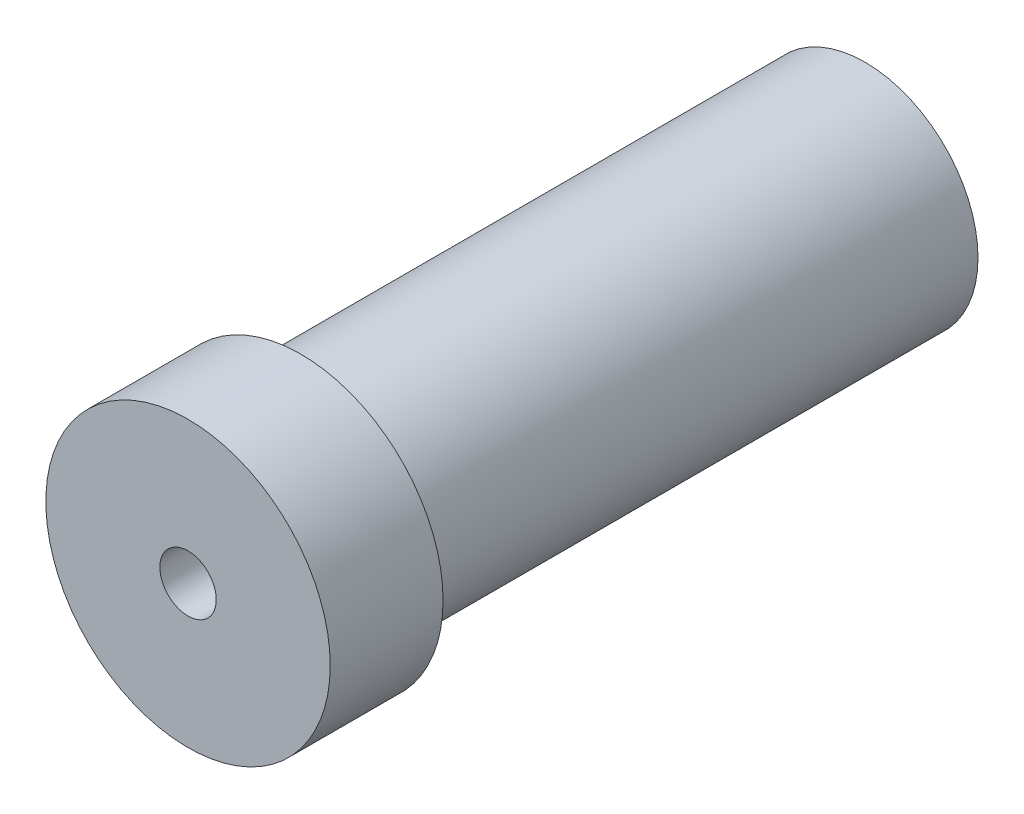
SolidWorks part; units mm, degrees
ref_plane "Front" through (0, 0, 0) normal (0, 0, 1) x (1, 0, 0)
ref_plane "Top" through (0, 0, 0) normal (0, 1, 0) x (1, 0, 0)
ref_plane "Right" through (0, 0, 0) normal (1, 0, 0) x (0, 0, -1)
sketch "Sketch3" plane through (0, 0, 0) normal (0, 0, 1) x (1, 0, 0)
  line L0 (0, -65.6804) -> (0, -71.4078) construction
  circle A0 centre (0, 0) radius 16.002
  circle A3 centre (0, 0) radius 3.175
  dimension "D1" = 32.004
  dimension "D2" = 6.35
extrude "Boss-Extrude1" add sketch "Sketch3" along normal blind 12.7
sketch "Sketch5" plane through (0, 0, 0) normal (0, 0, -1) x (-1, 0, 0)
  line L1 (0, 6.4158) -> (-5.5563, 3.2079)
  line L2 (-5.5563, 3.2079) -> (-5.5563, -3.2079)
  line L3 (-5.5563, -3.2079) -> (0, -6.4158)
  line L4 (0, -6.4158) -> (5.5562, -3.2079)
  line L5 (5.5562, -3.2079) -> (5.5562, 3.2079)
  line L6 (5.5562, 3.2079) -> (0, 6.4158)
  dimension "D1" = 11.1125
extrude "Cut-Extrude2" cut sketch "Sketch5" against normal blind 4.064
sketch "Sketch4" plane through (0, 0, 0) normal (0, 0, -1) x (-1, 0, 0)
  circle A1 centre (0, 0) radius 12.7
  circle A2 centre (0, 0) radius 9.525
  dimension "D1" = 25.4
  dimension "D2" = 19.05
extrude "Boss-Extrude2" add sketch "Sketch4" along normal blind 63.5
ref_plane "Plane1" through (0, 0, -38.1) normal (0, 0, -1) x (-1, 0, 0)
sketch "Sketch9" plane through (0, 0, 0) normal (1, 0, 0) x (0, 0, -1)
  circle A0 centre (38.1, 0) radius 2.5
  dimension "D2" = 5
  dimension "D1" = 38.1
